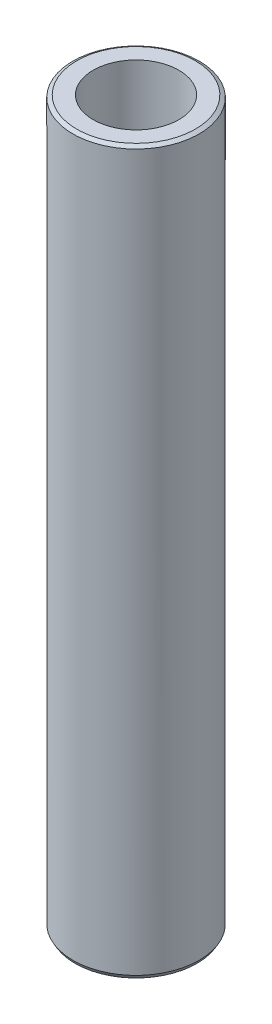
SolidWorks part; units mm, degrees
ref_plane "Front Plane" through (0, 0, 0) normal (0, 0, 1) x (1, 0, 0)
ref_plane "Top Plane" through (0, 0, 0) normal (0, 1, 0) x (1, 0, 0)
ref_plane "Right Plane" through (0, 0, 0) normal (1, 0, 0) x (0, 0, -1)
sketch "Sketch1" plane through (0, 0, 0) normal (0, 1, 0) x (1, 0, 0)
  circle A0 centre (0, 0) radius 52.5
  dimension "SHAFT_OD" = 105
extrude "Boss-Extrude1" add sketch "Sketch1" along normal blind 600
sketch "Sketch2" plane through (0, 0, 0) normal (0, 1, 0) x (1, 0, 0)
  circle A0 centre (0, 0) radius 35.6476
  dimension "BORE_D" = 71.2952
extrude "Cut-Extrude1" cut sketch "Sketch2" along normal through all
chamfer "Chamfer1" distance 1.8497 angle 60 2 edges at (0, 600, 52.5) (0, 0, 52.5) first distance on face at (0, 600, 52.5) first distance on face at (0, 0, 35.6476)
